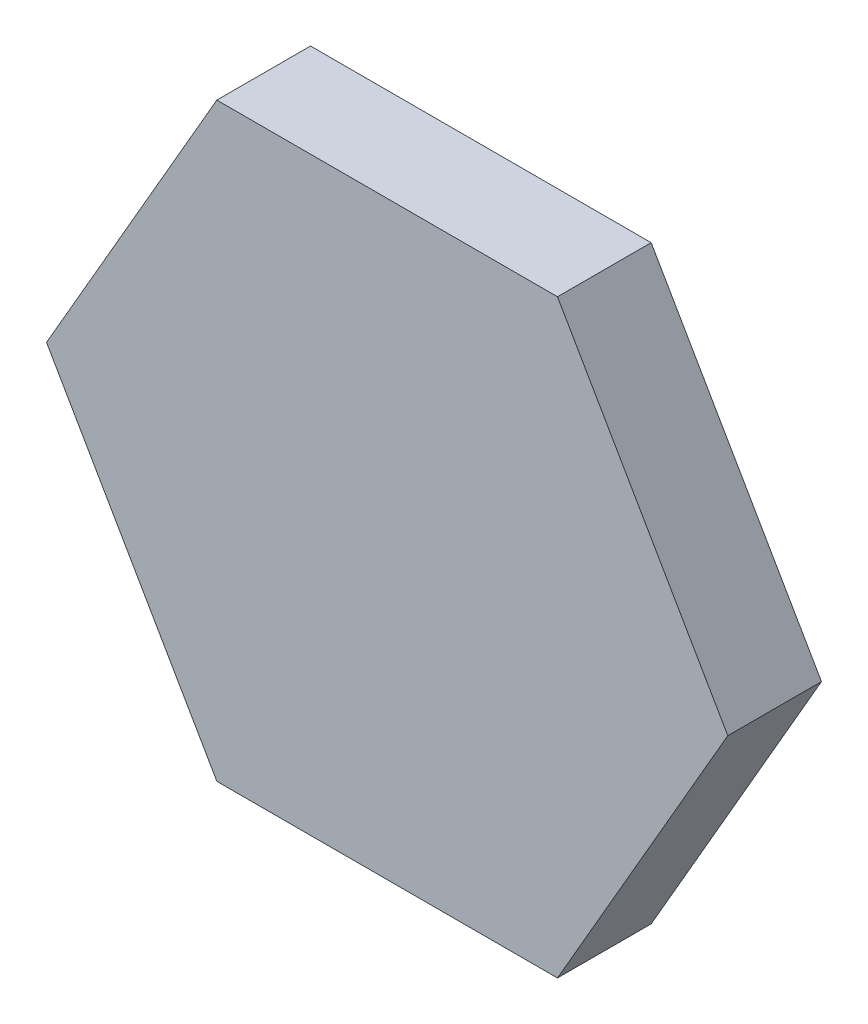
SolidWorks part; units mm, degrees
ref_plane "Plan de face" through (0, 0, 0) normal (0, 0, 1) x (1, 0, 0)
ref_plane "Plan de dessus" through (0, 0, 0) normal (0, 1, 0) x (1, 0, 0)
ref_plane "Plan de droite" through (0, 0, 0) normal (1, 0, 0) x (0, 0, -1)
sketch "Esquisse1" plane through (0, 0, 0) normal (0, 0, 1) x (1, 0, 0)
  line L0 (-30, -51.9615) -> (30, -51.9615)
  line L1 (60, 0) -> (30, 51.9615)
  line L2 (30, 51.9615) -> (-30, 51.9615)
  line L3 (-30, 51.9615) -> (-60, 0)
  line L4 (-60, 0) -> (-30, -51.9615)
  line L5 (30, -51.9615) -> (60, 0)
  circle A0 centre (0, 0) radius 51.9615 construction
  dimension "D1" = 60
  dimension "D2" = 103.923
extrude "Boss.-Extru.1" add sketch "Esquisse1" along normal blind 1.5
ref_plane "Plan1" through (-45, -25.9808, 0) normal (-0.866, -0.5, 0) x (0, 0, 1)
sketch "Esquisse3" plane through (-45, -25.9808, 0) normal (-0.866, -0.5, 0) x (0, 0, 1)
  line L1 (-15, 30) -> (-15, -30)
  line L2 (-15, -30) -> (0, -30)
  line L4 (0, 30) -> (-15, 30)
  line L5 (0, -30) -> (0, 30)
extrude "Boss.-Extru.2" add sketch "Esquisse3" against normal blind 1.5
ref_plane "Plan2" through (0, -51.9615, 0) normal (0, -1, 0) x (-1, 0, 0)
sketch "Esquisse5" plane through (0, -51.9615, 0) normal (0, -1, 0) x (-1, 0, 0)
  line L0 (-30, 0) -> (-30, 15)
  line L1 (-30, 15) -> (30, 15)
  line L2 (30, 15) -> (30, 0)
  line L3 (30, 0) -> (-30, 0)
extrude "Boss.-Extru.3" add sketch "Esquisse5" against normal blind 1.5
ref_plane "Plan3" through (45, -25.9808, 0) normal (0.866, -0.5, 0) x (0, 0, -1)
sketch "Esquisse6" plane through (45, -25.9808, 0) normal (0.866, -0.5, 0) x (0, 0, -1)
  line L0 (0, 30) -> (15, 30)
  line L1 (15, 30) -> (15, -30)
  line L2 (15, -30) -> (0, -30)
  line L3 (0, -30) -> (0, 30)
extrude "Boss.-Extru.4" add sketch "Esquisse6" against normal blind 1.5
ref_axis "Axe1" through (-60, 0, 0) along (1, 0, 0)
ref_plane "Plan4" through (0, 0, 0) normal (0, 1, 0) x (1, 0, 0)
mirror "Symétrie1" about plane through (0, 0, 0) normal (0, 1, 0) of "Boss.-Extru.4", "Boss.-Extru.3", "Boss.-Extru.2"
ref_plane "Plan5" through (0, 0, -15) normal (0, 0, -1) x (-1, 0, 0)
sketch "Esquisse7" plane through (0, 0, -15) normal (0, 0, -1) x (-1, 0, 0)
  line L1 (-59.5, 0) -> (-29.75, -51.5285)
  line L2 (-29.75, -51.5285) -> (29.75, -51.5285)
  line L3 (29.75, -51.5285) -> (59.5, 0)
  line L4 (59.5, 0) -> (29.75, 51.5285)
  line L5 (29.75, 51.5285) -> (-29.75, 51.5285)
  line L6 (-29.75, 51.5285) -> (-59.5, 0)
  circle A0 centre (0, 0) radius 51.5285 construction
  dimension "D1" = 0.5
extrude "Enlèv. mat.-Extru.1" cut sketch "Esquisse7" against normal blind 1
